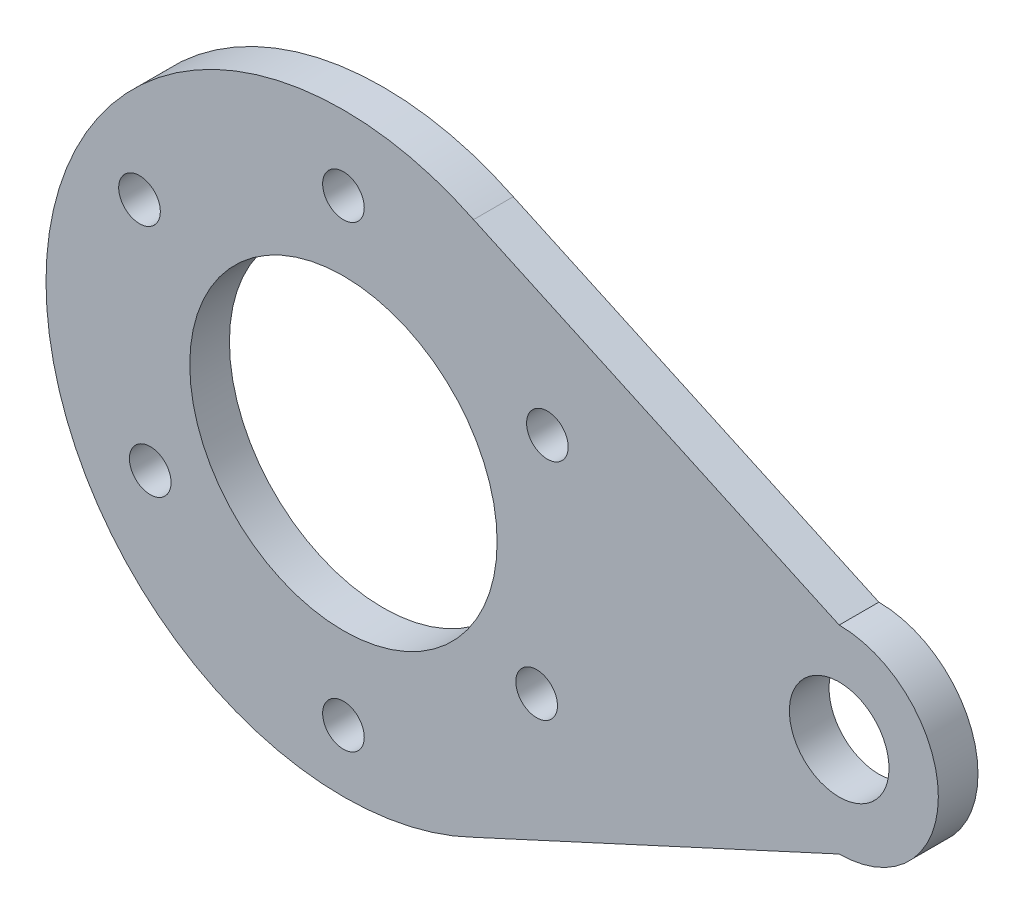
SolidWorks part; units mm, degrees
other "标注1"
sketch "草图3" plane through (-27.4259, -35.5276, 4) normal (0, 0, 1) x (1, 0, 0)
ref_plane "前视基准面" through (0, 0, 0) normal (0, 0, 1) x (1, 0, 0)
ref_plane "上视基准面" through (0, 0, 0) normal (0, 1, 0) x (1, 0, 0)
ref_plane "右视基准面" through (0, 0, 0) normal (1, 0, 0) x (0, 0, -1)
sketch "草图2" plane through (0, 0, 0) normal (0, 0, 1) x (1, 0, 0)
  line L0 (2.5741, -5.5276) -> (41.8465, -28.2015) construction
  line L1 (2.5741, -5.5276) -> (52.5741, -5.5276) construction
  line L5 (52.5741, 4.4724) -> (15.6991, 21.449)
  line L6 (15.6991, -32.5041) -> (52.5741, -15.5276)
  circle A0 centre (2.5741, -5.5276) radius 23.75 construction
  circle A1 centre (2.5741, -5.5276) radius 22.5 construction
  circle A2 centre (2.5741, -29.2776) radius 2.1
  circle A3 centre (22.0596, -16.7776) radius 2.1
  circle A4 centre (2.5741, -5.5276) radius 30 construction
  arc A5 (15.6991, 21.449) -> (15.6991, -32.5041) centre (2.5741, -5.5276) ccw
  circle A6 centre (2.5741, -5.5276) radius 15.5
  circle A11 centre (52.5741, -5.5276) radius 5.025
  circle A12 centre (52.5741, -5.5276) radius 10 construction
  arc A13 (52.5741, 4.4724) -> (52.5741, -15.5276) centre (52.5741, -5.5276) cw
  circle A14 centre (-17.994, 6.3474) radius 2.1
  circle A15 centre (23.1422, 6.3474) radius 2.1
  circle A16 centre (2.5741, 16.9724) radius 2.1
  circle A17 centre (-16.9115, -16.7776) radius 2.1
  dimension "D1" = 45
  dimension "D2" = 4.2
  dimension "D3" = 50
  dimension "D4" = 60
  dimension "D5" = 10.05
  dimension "D6" = 47.5
  dimension "D7" = 3
  dimension "D8" = 3
extrude "凸台-拉伸1" add sketch "草图2" along normal blind 4
